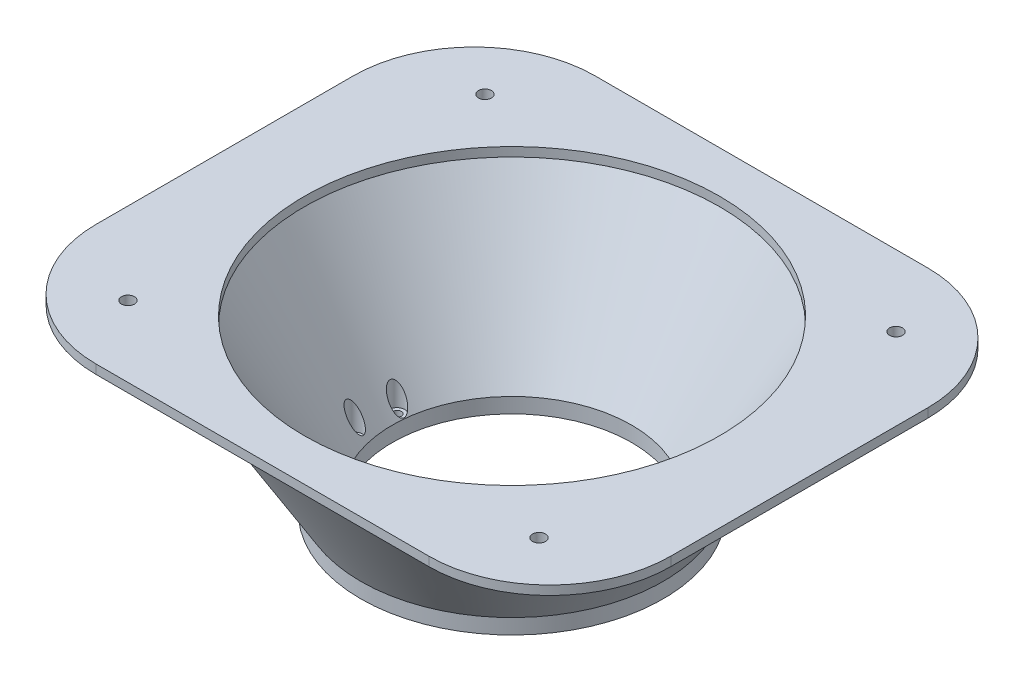
SolidWorks part; units mm, degrees
ref_plane "Front Plane" through (0, 0, 0) normal (0, 0, 1) x (1, 0, 0)
ref_plane "Top Plane" through (0, 0, 0) normal (0, 1, 0) x (1, 0, 0)
ref_plane "Right Plane" through (0, 0, 0) normal (1, 0, 0) x (0, 0, -1)
sketch "Sketch4" plane through (0, 0, 0) normal (0, 1, 0) x (1, 0, 0)
  line L0 (0, -45) -> (0, 45) construction
  circle A0 centre (0, 0) radius 39.565
  circle A1 centre (0, 0) radius 50
  circle A2 centre (42, -10) radius 1.4
  circle A3 centre (42, 4) radius 1.4
  circle A4 centre (-42, -10) radius 1.4
  circle A5 centre (-42, 4) radius 1.4
  point P5 (0, 0)
  point P14 (0, 0)
  point P15 (-2.3531, -0.9716)
  dimension "D1" = 79.13
  dimension "D3" = 100
  dimension "D4" = 2.8
  dimension "D2" = 90
extrude "Boss-Extrude3" add sketch "Sketch4" along normal blind 5
sketch "Sketch6" plane through (0, 0, 0) normal (1, 0, 0) x (0, 0, -1)
  line L0 (-50, 5) -> (-79.0628, 53)
  line L2 (-50, 5) -> (-39.565, 5)
  line L3 (-39.565, 5) -> (-68.6278, 53)
  line L5 (-68.6278, 53) -> (-79.0628, 53)
  point P3 (0, 0)
  dimension "D1" = 18.6278
  dimension "D2" = 48
ref_plane "Plane1" through (0, 15, 0) normal (0, 1, 0) x (1, 0, 0)
ref_axis "Axis1" through (0, 0, 0) along (0, 1, 0)
revolve "Revolve1" add sketch "Sketch6" angle 360 about axis through (0, 0, 0) along (0, 1, 0)
sketch "Sketch7" plane through (0, 53, 0) normal (0, 1, 0) x (1, 0, 0)
  line L1 (-95, 82.5) -> (95, 82.5)
  line L2 (-95, 82.5) -> (-95, -82.5)
  line L3 (-95, -82.5) -> (95, -82.5)
  line L4 (95, 82.5) -> (95, -82.5)
  line L5 (-95, 82.5) -> (95, -82.5) construction
  line L6 (-95, -82.5) -> (95, 82.5) construction
  circle A0 centre (0, 0) radius 68.6289
  circle A1 centre (-67.953, 59.0118) radius 2.15
  circle A2 centre (67.953, 59.0118) radius 2.15
  circle A3 centre (67.953, -59.0118) radius 2.15
  circle A4 centre (-67.953, -59.0118) radius 2.15
  point P4 (0, 0)
  point P16 (0, 0)
  point P17 (0, 0)
  dimension "D5" = 4.3
  dimension "D1" = 190
  dimension "D2" = 165
  dimension "D3" = 90
  dimension "D4" = 90
extrude "Boss-Extrude4" add sketch "Sketch7" along normal blind 3
fillet "Fillet1" radius 40 4 edges at (95, 54.5, -82.5) (95, 54.5, 82.5) (-95, 54.5, 82.5) (-95, 54.5, -82.5)
sketch "Sketch8" plane through (0, 0, 0) normal (0, -1, 0) x (1, 0, 0)
  circle A0 centre (42, 10) radius 2.5
  circle A1 centre (42, -4) radius 2.5
  circle A2 centre (-42, 10) radius 2.5
  circle A3 centre (-42, -4) radius 2.5
  dimension "D1" = 5
extrude "Cut-Extrude1" cut sketch "Sketch8" against normal through all from offset 5 offset against normal yes
